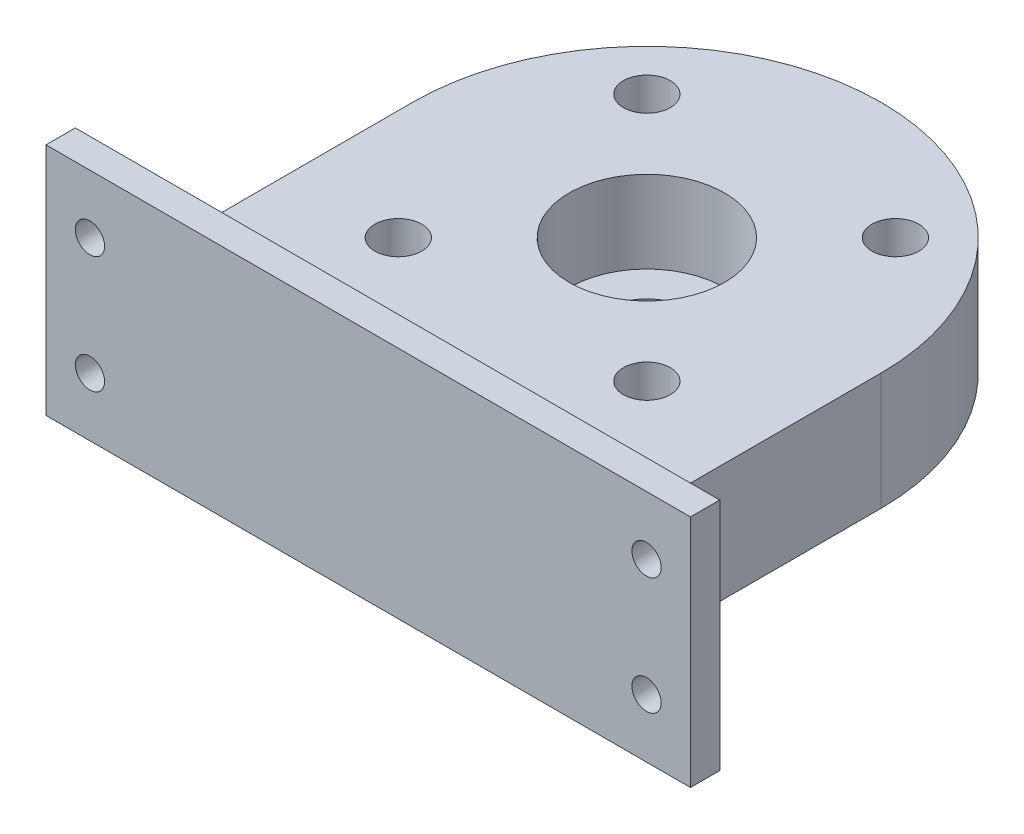
SolidWorks part; units mm, degrees
ref_plane "Front Plane" through (0, 0, 0) normal (0, 0, 1) x (1, 0, 0)
ref_plane "Top Plane" through (0, 0, 0) normal (0, 1, 0) x (1, 0, 0)
ref_plane "Right Plane" through (0, 0, 0) normal (1, 0, 0) x (0, 0, -1)
sketch "Sketch1" plane through (0, 0, 0) normal (0, 1, 0) x (1, 0, 0)
  line L0 (-55, -42.5568) -> (-40, -42.5568)
  line L1 (0, 44.4418) -> (0, -55.9757) construction
  line L2 (-40, 0) -> (-40, -42.5568)
  line L3 (40, 0) -> (40, -42.5568)
  line L4 (-55, -42.5568) -> (-55, -47.5568)
  line L5 (-55, -47.5568) -> (55, -47.5568)
  line L6 (55, -47.5568) -> (55, -42.5568)
  line L7 (40, -42.5568) -> (55, -42.5568)
  arc A0 (40, 0) -> (-40, 0) centre (0, 0) ccw
  circle A1 centre (0, 0) radius 7
  dimension "D1" = 80
  dimension "D2" = 14
  dimension "D3" = 110
  dimension "D4" = 5
extrude "Boss-Extrude1" add sketch "Sketch1" along normal blind 20
sketch "Sketch2" plane through (0, 20, 0) normal (0, 1, 0) x (1, 0, 0)
  circle A0 centre (0, 0) radius 13.25
  dimension "D1" = 26.5
extrude "Cut-Extrude1" cut sketch "Sketch2" against normal blind 14
sketch "Sketch3" plane through (0, 20, 0) normal (0, 1, 0) x (1, 0, 0)
  line L0 (0, 48.1938) -> (0, -53.492) construction
  line L1 (-34.8672, 34.8672) -> (0, 0) construction
  circle A0 centre (-21.2132, 21.2132) radius 4
  arc A1 (40, 0) -> (-40, 0) centre (0, 0) ccw construction
  circle A2 centre (21.2132, 21.2132) radius 4
  circle A3 centre (21.2132, -21.2132) radius 4
  circle A4 centre (-21.2132, -21.2132) radius 4
  point P20 (0, 0)
  dimension "D1" = 8
  dimension "D2" = 30
  dimension "D3" = 45
  dimension "D4" = 4
extrude "Cut-Extrude2" cut sketch "Sketch3" against normal through all
sketch "Sketch4" plane through (0, 0, 0) normal (0, -1, 0) x (1, 0, 0)
  line L1 (-55, 42.5568) -> (55, 42.5568)
  line L2 (-55, 42.5568) -> (-55, 47.5568)
  line L3 (-55, 47.5568) -> (55, 47.5568)
  line L4 (55, 42.5568) -> (55, 47.5568)
extrude "Boss-Extrude2" add sketch "Sketch4" along normal blind 10
sketch "Sketch5" plane through (0, 20, 0) normal (0, 1, 0) x (1, 0, 0)
  line L1 (-55, -47.5568) -> (55, -47.5568)
  line L2 (-55, -47.5568) -> (-55, -42.5568)
  line L3 (-55, -42.5568) -> (55, -42.5568)
  line L4 (55, -47.5568) -> (55, -42.5568)
extrude "Boss-Extrude3" add sketch "Sketch5" along normal blind 10
fillet "Fillet1" radius 10 4 edges at (-40, 10, 42.5568) (0, 0, 42.5568) (40, 10, 42.5568) (0, 20, 42.5568) first distance on face at (0, 10, 42.5568)
sketch "Sketch6" plane through (0, 0, 47.5568) normal (0, 0, 1) x (1, 0, 0)
  line L0 (-55, 10) -> (55, 10) construction
  line L1 (-55, 30) -> (-55, -10) construction
  line L2 (55, 30) -> (55, -10) construction
  line L3 (-55, 30) -> (55, 30) construction
  line L4 (0, 30) -> (0, -10) construction
  line L5 (55, -10) -> (-55, -10) construction
  circle A0 centre (-47.5, 20) radius 2.5
  circle A2 centre (-47.5, 0) radius 2.5
  circle A3 centre (47.5, 0) radius 2.5
  circle A4 centre (47.5, 20) radius 2.5
  dimension "D2" = 5
  dimension "D1" = 7.5
  dimension "D4" = 10
extrude "Cut-Extrude4" cut sketch "Sketch6" against normal through all
sketch "Sketch7" plane through (0, 0, 42.5568) normal (0, 0, -1) x (-1, 0, 0)
  circle A0 centre (-47.5, 20) radius 5
  circle A1 centre (-47.5, 0) radius 5
  circle A2 centre (47.5121, 20) radius 5
  circle A3 centre (47.5, 0) radius 5
  dimension "D1" = 10
sketch "Sketch8" plane through (0, 20, 0) normal (0, 1, 0) x (1, 0, 0)
  circle A0 centre (0, 0) radius 40
extrude "Cut-Extrude5" cut sketch "Sketch8" along normal through all
